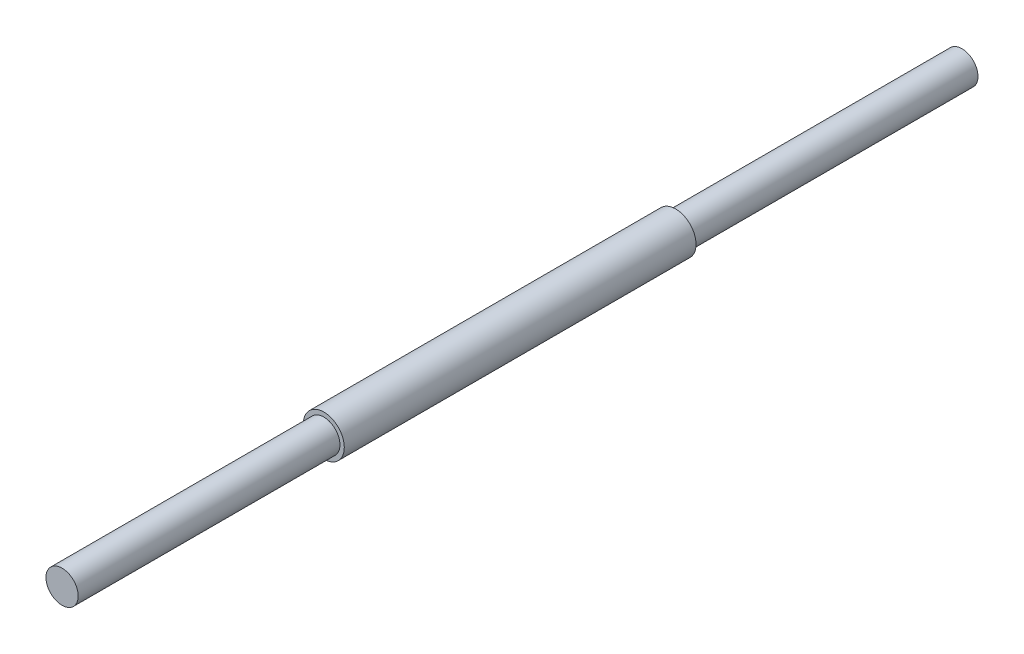
SolidWorks part; units mm, degrees
ref_plane "Front Plane" through (0, 0, 0) normal (0, 0, 1) x (1, 0, 0)
ref_plane "Top Plane" through (0, 0, 0) normal (0, 1, 0) x (1, 0, 0)
ref_plane "Right Plane" through (0, 0, 0) normal (1, 0, 0) x (0, 0, -1)
sketch "Sketch2" plane through (0, 0, 0) normal (0, 0, 1) x (1, 0, 0)
  circle A0 centre (0, 0) radius 2.5
  dimension "D1" = 5
extrude "Boss-Extrude1" add sketch "Sketch2" along normal blind 69.85 and the other way blind 69.85
sketch "Sketch3" plane through (0, 0, 0) normal (0, 0, 1) x (1, 0, 0)
  circle A0 centre (0, 0) radius 3.175
  dimension "D1" = 6.35
extrude "Boss-Extrude2" add sketch "Sketch3" along normal blind 29.21 and the other way blind 25.4
